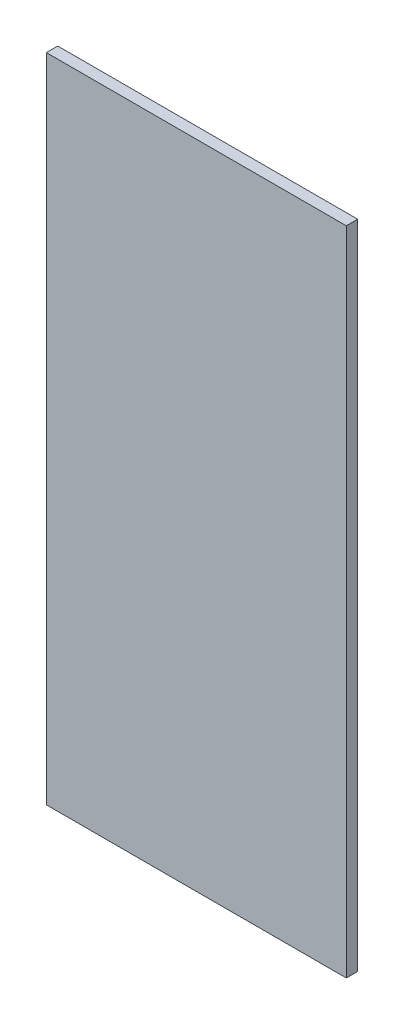
SolidWorks part; units mm, degrees
material "ABS"
ref_plane "X-Y Datum" through (0, 0, 0) normal (0, 0, 1) x (1, 0, 0)
ref_plane "X-Z Datum" through (0, 0, 0) normal (0, 1, 0) x (1, 0, 0)
ref_plane "Y-Z Datum" through (0, 0, 0) normal (1, 0, 0) x (0, 0, -1)
sketch "Sketch1" plane through (0, 0, 0) normal (0, 0, 1) x (1, 0, 0)
  line L1 (-41.8, 90.775) -> (41.8, 90.775)
  line L2 (-41.8, 90.775) -> (-41.8, -90.775)
  line L3 (-41.8, -90.775) -> (41.8, -90.775)
  line L4 (41.8, 90.775) -> (41.8, -90.775)
  line L5 (-41.8, 90.775) -> (41.8, -90.775) construction
  line L6 (-41.8, -90.775) -> (41.8, 90.775) construction
  point P0 (0, 0)
  dimension "D1" = 83.6
  dimension "D2" = 181.55
extrude "Boss-Extrude1" add sketch "Sketch1" along normal blind 3.175
